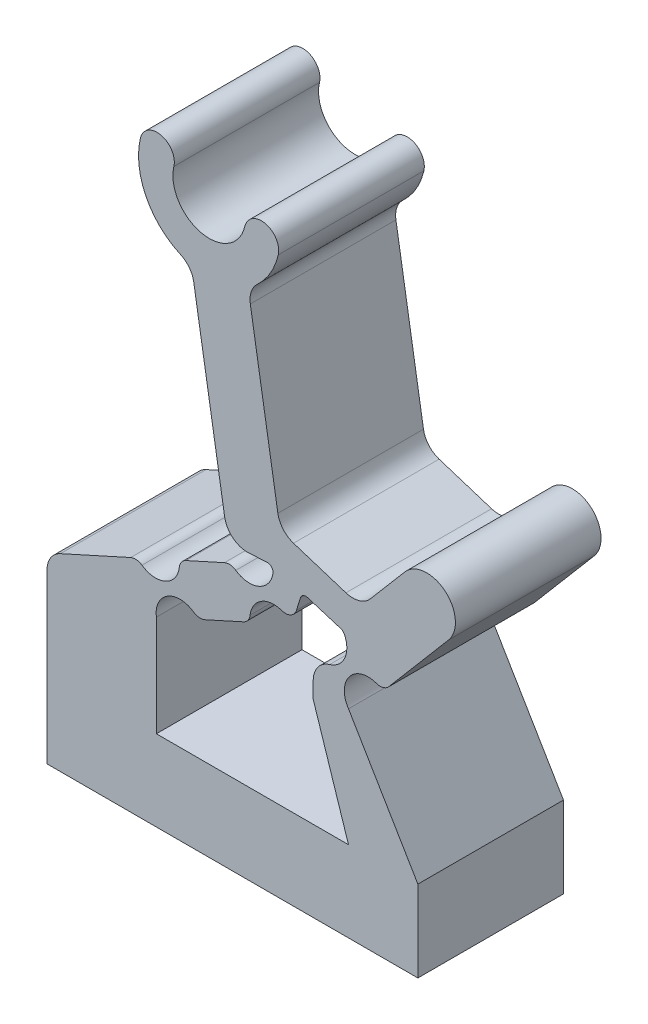
SolidWorks part; units mm, degrees
ref_plane "Front Plane" through (0, 0, 0) normal (0, 0, 1) x (1, 0, 0)
ref_plane "Top Plane" through (0, 0, 0) normal (0, 1, 0) x (1, 0, 0)
ref_plane "Right Plane" through (0, 0, 0) normal (1, 0, 0) x (0, 0, -1)
sketch "Sketch-SkeletonConfigUp" plane through (0, 0, 0) normal (0, 0, 1) x (1, 0, 0)
  line L0 (0, 0) -> (0, -50000) construction
  line L1 (0, 0) -> (5.2694, -4.2823) construction
  line L2 (16.5608, -13.4586) -> (13.0191, -3.4572) construction
  line L3 (13.0191, -3.4572) -> (9.3602, -2.4315) construction
  line L4 (9.3602, -2.4315) -> (5.2694, -4.2823) construction
  line L5 (13.0191, -3.4572) -> (16.5614, 0.711) construction
  line L6 (9.3602, -2.4315) -> (7.0797, 11.4322) construction
  line L7 (5.2694, -4.2823) -> (16.5608, -13.4586) construction
  line L8 (-768.3403, 624.4132) -> (16.5608, -13.4586) construction
  dimension "D2" = 6.79
  dimension "D3" = 14.55
  dimension "D4" = 10.61
  dimension "D5" = 148.6
  dimension "D6" = 3.8
  dimension "D7" = 5.47
  dimension "D8" = 14.05
  dimension "D9" = 4.49
  dimension "D10" = 65.3
  dimension "D11" = 65
  dimension "D12" = 50.9
sketch "Sketch-SkeletonConfigDown" plane through (0, 0, 0) normal (0, 0, 1) x (1, 0, 0)
  line L0 (0, 0) -> (0, -50000) construction
  line L1 (0, 0) -> (5.2694, -4.2823) construction
  line L2 (16.5608, -13.4586) -> (13.0191, -3.4572) construction
  line L3 (13.0191, -3.4572) -> (9.6581, -5.2302) construction
  line L4 (9.6581, -5.2302) -> (5.2694, -4.2823) construction
  line L5 (13.0191, -3.4572) -> (12.7221, 2.0047) construction
  line L6 (9.6581, -5.2302) -> (-1.5351, 3.2618) construction
  line L7 (5.2694, -4.2823) -> (16.5608, -13.4586) construction
  line L8 (-771.7106, 627.1522) -> (16.5608, -13.4586) construction
  dimension "D2" = 6.79
  dimension "D3" = 14.55
  dimension "D4" = 10.61
  dimension "D5" = 148.6
  dimension "D6" = 3.8
  dimension "D7" = 5.47
  dimension "D8" = 14.05
  dimension "D9" = 4.49
  dimension "D10" = 65.3
  dimension "D11" = 65
  dimension "D1" = 50.9
sketch "Sketch-ConfigUp" plane through (0, 0, 0) normal (0, 0, 1) x (1, 0, 0)
  line L1 (8.0369, -1.9326) -> (5.7683, -2.959)
  line L4 (9.3602, -2.4315) -> (5.2694, -4.2823) construction
  line L5 (15.6089, 1.5204) -> (13.672, -0.7587)
  line L6 (5.2694, -4.2823) -> (16.5608, -13.4586) construction
  line L9 (13.0191, -3.4572) -> (9.3602, -2.4315) construction
  line L10 (9.8591, -1.1082) -> (7.8943, -1.2211)
  line L11 (6.9026, -2.4458) -> (7.727, -4.268) construction
  line L16 (13.1482, -4.8792) -> (14.4287, -3.3428) construction
  line L17 (17.5139, -0.0985) -> (14.6492, -3.4694)
  line L18 (13.0191, -3.4572) -> (16.5614, 0.711) construction
  line L19 (15.6013, 1.5115) -> (17.5063, -0.1075) construction
  line L20 (6.3045, 8.4436) -> (7.8943, -1.2211)
  line L21 (10.1678, 0.3596) -> (8.7714, 8.8493)
  line L22 (9.3602, -2.4315) -> (7.0797, 11.4322) construction
  line L23 (6.0231, 10.1543) -> (8.49, 10.5601) construction
  line L26 (12.3716, -4.2192) -> (9.4385, -7.6705) construction
  line L27 (-155977.6217, 126759.5747) -> (16.5608, -13.4586) construction
  line L30 (10.3474, -5.0569) -> (11.8714, -6.352) construction
  line L38 (5.5133, 11.1745) -> (7.0797, 11.4322) construction
  line L39 (7.0797, 11.4322) -> (10.0861, 10.7293) construction
  line L42 (7.2022, -8.5173) -> (7.2022, -13.5356) construction
  line L43 (12.9047, -2.0476) -> (14.4287, -3.3428) construction
  line L44 (6.1805, -3.8701) -> (4.3583, -4.6945) construction
  line L46 (6.5926, -4.7812) -> (4.7705, -5.6056) construction
  line L47 (11.6096, -3.5716) -> (13.1482, -4.8792) construction
  line L51 (9.2571, -2.2038) -> (9.4632, -2.6593) construction
  line L52 (8.0369, -1.9326) -> (8.8613, -3.7548) construction
  line L53 (9.8591, -1.1082) -> (10.6835, -2.9304) construction
  line L54 (6.1549, -10.0136) -> (6.1549, -13.5356) construction
  line L56 (8.4491, -2.8437) -> (10.2713, -2.0193) construction
  line L59 (9.8591, -1.1082) -> (8.0369, -1.9326) construction
  line L61 (8.8613, -3.7548) -> (6.5926, -4.7812)
  line L62 (5.7683, -2.959) -> (6.5926, -4.7812) construction
  line L67 (7.0797, 11.4322) -> (4.0733, 12.135) construction
  line L69 (13.2096, -3.6191) -> (12.8286, -3.2953) construction
  line L71 (14.4287, -3.3428) -> (15.9709, -1.4924) construction
  line L73 (5.7683, -2.959) -> (3.9461, -3.7834) construction
  line L77 (9.4385, -7.6705) -> (16.5608, -13.4586) construction
  line L79 (10.1678, 0.3596) -> (13.672, -0.7587)
  line L81 (12.3716, -4.2192) -> (13.6667, -2.6952) construction
  line L82 (15.6013, 1.5115) -> (13.672, -0.7587) construction
  line L93 (5.1663, -4.0545) -> (5.3724, -4.5101) construction
  line L108 (0, -5.5687) -> (0, -13.5356)
  line L109 (0, -13.5356) -> (13.1482, -13.5356)
  line L115 (3.9461, -3.7834) -> (0, -5.5687)
  line L117 (11.6096, -3.5716) -> (12.9047, -2.0476) construction
  line L121 (10.6835, -2.9304) -> (8.8613, -3.7548) construction
  line L125 (4.7705, -5.6056) -> (4.7705, -10.0136)
  line L128 (10.1678, 0.3596) -> (10.7236, -3.0193) construction
  line L129 (3.9461, -3.7834) -> (4.7705, -5.6056) construction
  line L131 (0, -10.0136) -> (16.1878, -10.0136) construction
  line L132 (0, 200000) -> (0, -250000) construction
  line L133 (13.1482, -4.8792) -> (13.1482, -10.0136) construction
  line L134 (11.6096, -3.5716) -> (11.6096, -5.2903)
  line L135 (11.6096, -10.0136) -> (6.1549, -10.0136)
  line L136 (13.1482, -10.0136) -> (13.1482, -13.5356) construction
  line L137 (4.7705, -10.0136) -> (6.1549, -10.0136)
  line L138 (13.672, -0.7587) -> (12.9047, -2.0476) construction
  line L139 (9.8591, -1.1082) -> (10.1678, 0.3596) construction
  line L140 (13.1482, -4.8792) -> (16.1741, -9.9904)
  line L141 (16.1741, -9.9904) -> (16.1741, -13.5356)
  line L142 (16.1741, -13.5356) -> (13.1482, -13.5356)
  line L143 (11.6096, -5.2903) -> (13.1482, -10.0136)
  line L144 (13.1482, -10.0136) -> (11.6096, -10.0136)
  line L145 (11.6096, -5.2903) -> (11.6096, -10.0136) construction
  line L146 (9.8591, -1.1082) -> (12.9047, -2.0476) construction
  line L147 (10.6835, -2.9304) -> (11.1251, -1.4987)
  line L148 (11.1251, -1.4987) -> (12.9047, -2.0476)
  arc A0 (15.6089, 1.5204) -> (17.5139, -0.0985) centre (16.5614, 0.711) cw
  arc A2 (5.5339, 11.7936) -> (8.6255, 11.0708) centre (7.0797, 11.4322) ccw
  arc A3 (8.7714, 8.8493) -> (10.0861, 10.7293) centre (7.0797, 11.4322) ccw
  arc A4 (4.0733, 12.135) -> (5.5339, 11.7936) centre (4.8036, 11.9643) cw
  arc A5 (10.0861, 10.7293) -> (8.6255, 11.0708) centre (9.3558, 10.9) ccw
  arc A6 (4.0733, 12.135) -> (6.3045, 8.4436) centre (7.0797, 11.4322) ccw
  arc A7 (8.8613, -3.7548) -> (10.6835, -2.9304) centre (9.8926, -3.6084) cw
  arc A15 (6.5926, -4.7812) -> (4.7705, -5.6056) centre (5.8018, -5.4591) ccw
  arc A21 (8.0369, -1.9326) -> (9.8591, -1.1082) centre (8.8278, -1.2547) ccw
  arc A42 (5.7683, -2.959) -> (3.9461, -3.7834) centre (4.7369, -3.1055) cw
  arc A43 (13.1482, -4.8792) -> (14.6492, -3.4694) centre (14.0069, -4.2895) cw
  arc A44 (11.6096, -3.5716) -> (12.9047, -2.0476) centre (12.0349, -2.6207) ccw
  point P27 (7.3148, -3.3569)
  point P38 (16.5538, 0.702)
  point P51 (7.2565, 10.3572)
  point P61 (11.1094, -5.7044)
  point P125 (5.3724, -4.5101)
  point P130 (5.1663, -4.0545)
  dimension "D3" = 3.175
  dimension "D4" = 6.175
  dimension "D5" = 1.5
  dimension "D6" = 2
  dimension "D8" = 1.5
  dimension "D10" = 2
  dimension "D14" = 22.5
  dimension "D16" = 2.5
  dimension "D21" = 22.5
  dimension "D11" = 0.5
  dimension "D7" = 0.5
  dimension "D9" = 2
  dimension "D22" = 2
  dimension "D24" = 0.5
extrude "Boss-ConfigUp" add sketch "Sketch-ConfigUp" along normal blind 6.35
fillet "Fillet1" radius 1 6 edges at (8.7714, 8.8493, 3.175) (6.3045, 8.4436, 3.175) (0, -5.5687, 3.175) (13.672, -0.7587, 3.175) (10.1678, 0.3596, 3.175) (7.8943, -1.2211, 3.175)
fillet "Fillet2" radius 1 1 edges at (11.6096, -3.5716, 3.175)
fillet "Fillet3" radius 0.5 7 edges at (14.6492, -3.4694, 3.175) (3.9461, -3.7834, 3.175) (6.5926, -4.7812, 3.175) (8.8613, -3.7548, 3.175) (8.0369, -1.9326, 3.175) (5.7683, -2.959, 3.175) (10.6835, -2.9304, 3.175)
fillet "Fillet4" radius 0.25 3 edges at (9.8591, -1.1082, 3.175) (12.9047, -2.0476, 3.175) (11.1251, -1.4987, 3.175)
equation "\"axle-diameter\"=2"
equation "\"switch-thickness\"=12"
equation "\"base-width\"=4.0"
equation "\"axle-bushing-radius\"=3"
equation "\"clearance\"= 0.25"
equation "\"arm-width\"=1.5"
equation "\"min-diameter\"=70"
equation "\"alpha\"=50.9"
equation "\"beta\"=26.83"
equation "\"gamma\"=148.6"
equation "\"delta\"=65.0"
equation "\"epsilon\"=65.3"
equation "\"eta\"=-261.68"
equation "\"l_AB\"=14.55"
equation "\"l_AC\"=4.49"
equation "\"l_BD\"=10.61"
equation "\"l_CD\"=3.80"
equation "\"l_CE\"=14.05"
equation "\"l_DF\"=5.47"
equation "\"l_OA\"=6.79"
equation "\"D2@Sketch-SkeletonConfigUp\" = \"l_OA\""
equation "\"D3@Sketch-SkeletonConfigUp\" = \"l_AB\""
equation "\"D4@Sketch-SkeletonConfigUp\" = \"l_BD\""
equation "\"D5@Sketch-SkeletonConfigUp\" = \"gamma\""
equation "\"D6@Sketch-SkeletonConfigUp\" = \"l_CD\""
equation "\"D7@Sketch-SkeletonConfigUp\" = \"l_DF\""
equation "\"D8@Sketch-SkeletonConfigUp\" = \"l_CE\""
equation "\"D9@Sketch-SkeletonConfigUp\" = \"l_AC\""
equation "\"D_groove\"=3.175"
equation "\"D7@Sketch-SkeletonConfigDown\" = \"l_DF\""
equation "\"D6@Sketch-SkeletonConfigDown\" = \"l_CD\""
equation "\"D2@Sketch-SkeletonConfigDown\" = \"l_OA\""
equation "\"D3@Sketch-SkeletonConfigDown\" = \"l_AB\""
equation "\"D9@Sketch-SkeletonConfigDown\" = \"l_AC\""
equation "\"D8@Sketch-SkeletonConfigDown\" = \"l_CE\""
equation "\"D5@Sketch-SkeletonConfigDown\" = \"gamma\""
equation "\"D4@Sketch-SkeletonConfigDown\" = \"l_BD\""
equation "\"D1@Sketch-SkeletonConfigDown\" = \"alpha\""
equation "\"hinge_length\"=1.5"
equation "\"hinge_depth\"=0.25"
equation "\"D10@Sketch-SkeletonConfigUp\"=\"epsilon\""
equation "\"D11@Sketch-SkeletonConfigUp\"=\"delta\""
equation "\"D12@Sketch-SkeletonConfigUp\"=\"alpha\""
equation "\"D11@Sketch-SkeletonConfigDown\"=\"delta\""
equation "\"D10@Sketch-SkeletonConfigDown\"=\"epsilon\""
equation "\"EE_dx\"=8.64"
equation "\"EE_dy\"=8.19"
equation "\"r_groove\"=\"D_groove\"/2"
equation "\"t_wall\"=25.4/16"
equation "\"width_lower\"=\"D_groove\"+\"t_wall\""
equation "\"cable_to_bottom\"=30.6257"
